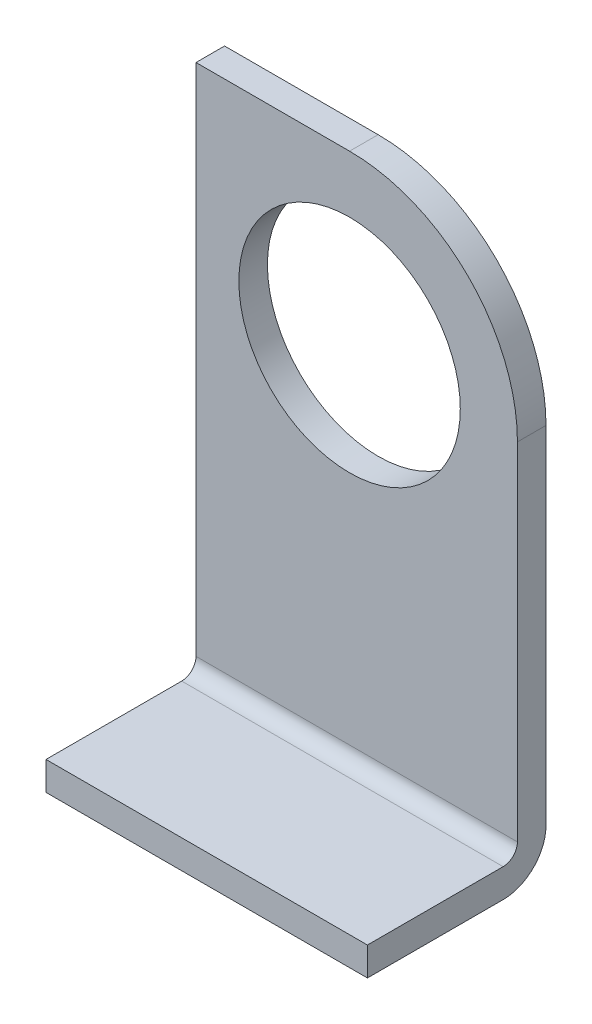
SolidWorks part; units mm, degrees
ref_plane "Front Plane" through (0, 0, 0) normal (0, 0, 1) x (1, 0, 0)
ref_plane "Top Plane" through (0, 0, 0) normal (0, 1, 0) x (1, 0, 0)
ref_plane "Right Plane" through (0, 0, 0) normal (1, 0, 0) x (0, 0, -1)
sketch "Sketch1" plane through (0, 0, 0) normal (0, 1, 0) x (1, 0, 0)
  line L1 (0, 0) -> (22.5, 0)
  line L2 (0, 0) -> (0, 12.5)
  line L3 (0, 12.5) -> (22.5, 12.5)
  line L4 (22.5, 0) -> (22.5, 12.5)
  dimension "D1" = 12.5
  dimension "D2" = 22.5
extrude "Boss-Extrude1" add sketch "Sketch1" along normal blind 2
sketch "Sketch2" plane through (0, 0, -12.5) normal (0, 0, -1) x (-1, 0, 0)
  line L1 (-22.5, 2) -> (0, 2)
  line L2 (-22.5, 2) -> (-22.5, 39)
  line L3 (-22.5, 39) -> (0, 39)
  line L4 (0, 2) -> (0, 39)
  dimension "D1" = 37
extrude "Boss-Extrude2" add sketch "Sketch2" against normal blind 2
fillet "Fillet1" radius 1 1 edges at (11.25, 2, -10.5)
fillet "Fillet2" radius 3 1 edges at (11.25, 0, -12.5)
sketch "Sketch5" plane through (0, 0, -12.5) normal (0, 0, -1) x (-1, 0, 0)
  line L1 (-22.5, 39) -> (-22.5, 3) construction
  line L2 (0, 39) -> (-22.5, 39) construction
  circle A0 centre (-10.75, 27.25) radius 7.75
  dimension "D1" = 4
  dimension "D2" = 4
  dimension "D3" = 15.5
extrude "Cut-Extrude1" cut sketch "Sketch5" against normal blind 2 contours A0
sketch "Sketch6" plane through (0, 0, -12.5) normal (0, 0, -1) x (-1, 0, 0)
  line L0 (-22.5, 39) -> (-22.5, 3) construction
  line L1 (0, 39) -> (-22.5, 39) construction
  arc A0 (-22.5, 27.25) -> (-10.75, 39) centre (-10.75, 27.25) cw
extrude "Cut-Extrude2" cut sketch "Sketch6" against normal blind 2 and the other way through all
sketch "Sketch9" plane through (0, 0, -12.5) normal (0, 0, -1) x (-1, 0, 0)
  line L0 (0, 39) -> (0, 3) construction
  arc A0 (-10.75, 39) -> (0, 31.9934) centre (-10.75, 27.25) cw
  arc A1 (-10.75, 39) -> (-22.5, 27.25) centre (-10.75, 27.25) ccw construction
  point P9 (0, 0)
sketch "Sketch13" plane through (0, 0, -12.5) normal (0, 0, -1) x (-1, 0, 0)
  line L0 (0, 39) -> (0, 3) construction
  arc A0 (-1.0377, 33.8631) -> (0, 33.3143) centre (0, 34.5697) ccw
  arc A1 (0, 31.9934) -> (-10.75, 39) centre (-10.75, 27.25) ccw construction
